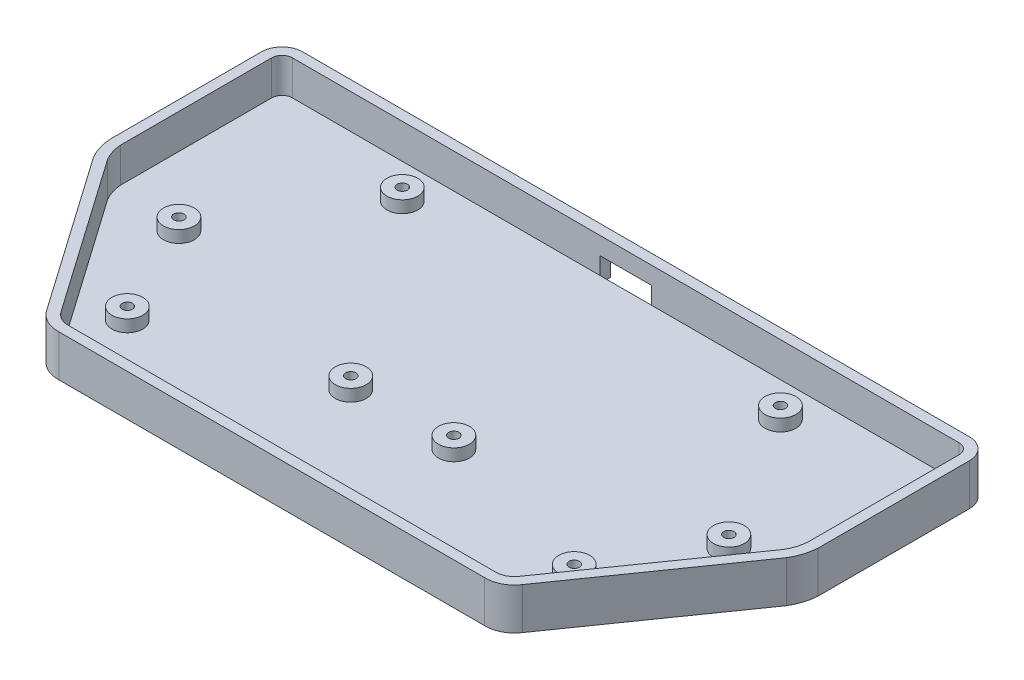
SolidWorks part; units mm, degrees
ref_plane "前视基准面" through (0, 0, 0) normal (0, 0, 1) x (1, 0, 0)
ref_plane "上视基准面" through (0, 0, 0) normal (0, 1, 0) x (1, 0, 0)
ref_plane "右视基准面" through (0, 0, 0) normal (1, 0, 0) x (0, 0, -1)
other "Configuration Table"
sketch "草图1" plane through (0, 0, 0) normal (0, 1, 0) x (1, 0, 0)
  line L0 (0, 0) -> (0, -3) construction
  line L1 (0, -3) -> (3, -3) construction
  line L2 (0, 0) -> (3, 0) construction
  line L3 (0, -3) -> (0, -47)
  line L4 (0, -47) -> (0, -50) construction
  line L5 (0, -50) -> (0, -100) construction
  line L6 (0, -100) -> (35, -100) construction
  line L7 (0, -50) -> (35, -100) construction
  line L8 (35, -100) -> (38, -100) construction
  line L9 (33.2796, -97.5423) -> (1.7204, -52.4577)
  line L10 (38, -100) -> (162, -100)
  line L11 (162, -100) -> (165, -100) construction
  line L12 (165, -100) -> (200, -100) construction
  line L13 (200, -100) -> (200, -50) construction
  line L14 (200, -50) -> (165, -100) construction
  line L15 (200, -50) -> (200, -47) construction
  line L16 (198.2796, -52.4577) -> (166.7204, -97.5423)
  line L17 (200, -47) -> (200, -3)
  line L18 (200, -3) -> (200, 0) construction
  line L19 (200, -3) -> (197, -3) construction
  line L20 (200, 0) -> (197, 0) construction
  line L21 (197, 0) -> (3, 0)
  line L22 (197, 3) -> (3, 3)
  line L23 (-3, -3) -> (-3, -47.1005)
  line L24 (30.7969, -99.2269) -> (-0.7949, -54.0957)
  line L25 (38.0436, -103) -> (161.9564, -103)
  line L26 (200.7949, -54.0957) -> (169.2031, -99.2269)
  line L27 (203, -47.1005) -> (203, -3)
  arc A0 (0, -3) -> (3, 0) centre (3, -3) cw
  arc A1 (0, -47) -> (1.7204, -52.4577) centre (0, -50) cw construction
  arc A2 (0, -47) -> (1.7204, -52.4577) centre (2.8612, -49.0981) cw construction
  arc A3 (0, -47) -> (1.7204, -52.4577) centre (6.2451, -48.0314) cw construction
  arc A4 (0, -47) -> (1.7204, -52.4577) centre (12.282, -46.1284) ccw
  arc A5 (38, -100) -> (33.2796, -97.5423) centre (35, -100) ccw construction
  arc A6 (38, -100) -> (33.2796, -97.5423) centre (36.3854, -97.3391) ccw construction
  arc A7 (38, -100) -> (33.2796, -97.5423) centre (37.8228, -94.5784) cw
  arc A8 (162, -100) -> (166.7204, -97.5423) centre (165, -100) cw construction
  arc A9 (162, -100) -> (166.7204, -97.5423) centre (163.6146, -97.3391) cw construction
  arc A10 (162, -100) -> (166.7204, -97.5423) centre (162.1772, -94.5784) ccw
  arc A11 (200, -47) -> (198.2796, -52.4577) centre (200, -50) ccw construction
  arc A12 (200, -47) -> (198.2796, -52.4577) centre (197.1388, -49.0981) ccw construction
  arc A13 (200, -47) -> (198.2796, -52.4577) centre (193.7549, -48.0314) ccw construction
  arc A14 (200, -47) -> (198.2796, -52.4577) centre (187.718, -46.1284) cw
  arc A15 (200, -3) -> (197, 0) centre (197, -3) ccw
  arc A16 (-3, -3) -> (3, 3) centre (3, -3) cw
  arc A17 (-3, -47.1005) -> (-0.7949, -54.0957) centre (12.282, -46.1284) ccw
  arc A18 (38.0436, -103) -> (30.7969, -99.2269) centre (37.8228, -94.5784) cw
  arc A19 (161.9564, -103) -> (169.2031, -99.2269) centre (162.1772, -94.5784) ccw
  arc A20 (203, -47.1005) -> (200.7949, -54.0957) centre (187.718, -46.1284) cw
  arc A21 (203, -3) -> (197, 3) centre (197, -3) ccw
  dimension "D1" = 3
  dimension "D2" = 3
  dimension "D3" = 3
  dimension "D4" = 44
  dimension "D5" = 3
  dimension "D6" = 50
  dimension "D7" = 35
  dimension "D8" = 3
  dimension "D9" = 124
  dimension "D10" = 3
  dimension "D11" = 35
  dimension "D12" = 50
  dimension "D13" = 3
  dimension "D14" = 44
  dimension "D15" = 3
  dimension "D16" = 3
  dimension "D17" = 3
  dimension "D18" = 3
extrude "凸台-拉伸1" add sketch "草图1" against normal blind 2 contours L22 A16 L23 A17 L24 A18 L25 A19 L26 A20 L27 A21
extrude "凸台-拉伸2" add sketch "草图1<3>" along normal blind 10.1
sketch "草图1<3>" plane through (0, 0, 0) normal (0, 1, 0) x (1, 0, 0) same geometry as "草图1"
sketch "草图3" plane through (0, 0, 0) normal (0, 1, 0) x (1, 0, 0)
  line L0 (0, 0) -> (200, 0) construction
  line L1 (200, 0) -> (200, -100) construction
  line L2 (200, -100) -> (0, -100) construction
  line L3 (0, -100) -> (0, 0) construction
  line L4 (0, -100) -> (35, -100) construction
  line L5 (200, -100) -> (165, -100) construction
  line L6 (200, -50) -> (165, -100) construction
  line L7 (0, -50) -> (35, -100) construction
  line L8 (0, 0) -> (45, 0) construction
  line L9 (45, 0) -> (45, -10) construction
  line L10 (200, 0) -> (155, 0) construction
  line L11 (155, 0) -> (155, -10) construction
  line L12 (200, -50) -> (180, -50) construction
  line L13 (0, -50) -> (20, -50) construction
  line L14 (35, -100) -> (35, -80) construction
  line L15 (165, -100) -> (165, -80) construction
  line L16 (35, -80) -> (35, -65) construction
  line L17 (35, -65) -> (85, -65) construction
  line L18 (165, -80) -> (165, -65) construction
  line L19 (165, -65) -> (115, -65) construction
  circle A0 centre (45, -10) radius 1.5
  circle A1 centre (20, -50) radius 1.5
  circle A2 centre (35, -80) radius 1.5
  circle A3 centre (85, -65) radius 1.5
  circle A4 centre (155, -10) radius 1.5
  circle A5 centre (180, -50) radius 1.5
  circle A6 centre (165, -80) radius 1.5
  circle A7 centre (115, -65) radius 1.5
  dimension "D16" = 3
  dimension "D17" = 3
  dimension "D18" = 3
  dimension "D19" = 3
  dimension "D20" = 3
  dimension "D21" = 3
  dimension "D22" = 3
  dimension "D23" = 3
  dimension "D1" = 200
  dimension "D2" = 100
  dimension "D3" = 35
  dimension "D4" = 35
  dimension "D5" = 45
  dimension "D6" = 10
  dimension "D7" = 45
  dimension "D8" = 10
  dimension "D9" = 20
  dimension "D10" = 20
  dimension "D11" = 20
  dimension "D12" = 20
  dimension "D13" = 15
  dimension "D14" = 50
  dimension "D15" = 50
extrude "切除-拉伸1" cut sketch "草图3" against normal through all
sketch "草图6" plane through (0, 0, 0) normal (0, 1, 0) x (1, 0, 0)
  circle A0 centre (180, -50) radius 1.5 construction
  circle A1 centre (155, -10) radius 1.5 construction
  circle A2 centre (165, -80) radius 1.5 construction
  circle A3 centre (115, -65) radius 1.5 construction
  circle A4 centre (85, -65) radius 1.5 construction
  circle A5 centre (35, -80) radius 1.5 construction
  circle A6 centre (20, -50) radius 1.5 construction
  circle A7 centre (45, -10) radius 1.5 construction
  circle A8 centre (180, -50) radius 1.5
  circle A9 centre (155, -10) radius 1.5
  circle A10 centre (165, -80) radius 1.5
  circle A11 centre (115, -65) radius 1.5
  circle A12 centre (85, -65) radius 1.5
  circle A13 centre (35, -80) radius 1.5
  circle A14 centre (20, -50) radius 1.5
  circle A15 centre (45, -10) radius 1.5
  circle A16 centre (85, -65) radius 4.5
  circle A17 centre (35, -80) radius 4.5
  circle A18 centre (20, -50) radius 4.5
  circle A19 centre (45, -10) radius 4.5
  circle A20 centre (155, -10) radius 4.5
  circle A21 centre (115, -65) radius 4.5
  circle A22 centre (180, -50) radius 4.5
  circle A23 centre (165, -80) radius 4.5
  dimension "D1" = 3
extrude "凸台-拉伸3" add sketch "草图6" along normal blind 3.5
ref_plane "基准面1" through (0, 0, -3) normal (0, 0, -1) x (-1, 0, 0)
sketch "草图7" plane through (0, 0, -3) normal (0, 0, -1) x (-1, 0, 0)
  line L0 (0, 0) -> (0, -2) construction
  line L1 (-30.7969, -2) -> (0.7949, -2) construction
  line L2 (0, -2) -> (-100, -2) construction
  line L3 (-38.0436, -2) -> (-161.9564, -2) construction
  line L4 (-107.5, -2) -> (-92.5, -2)
  line L5 (-197, -2) -> (-3, -2) construction
  line L6 (-107.5, -2) -> (-107.5, 5)
  line L7 (-107.5, 5) -> (-92.5, 5)
  line L8 (-92.5, 5) -> (-92.5, -2)
  point P11 (-100, -2)
  dimension "D1" = 15
  dimension "D2" = 7
extrude "切除-拉伸2" cut sketch "草图7" against normal blind 3
